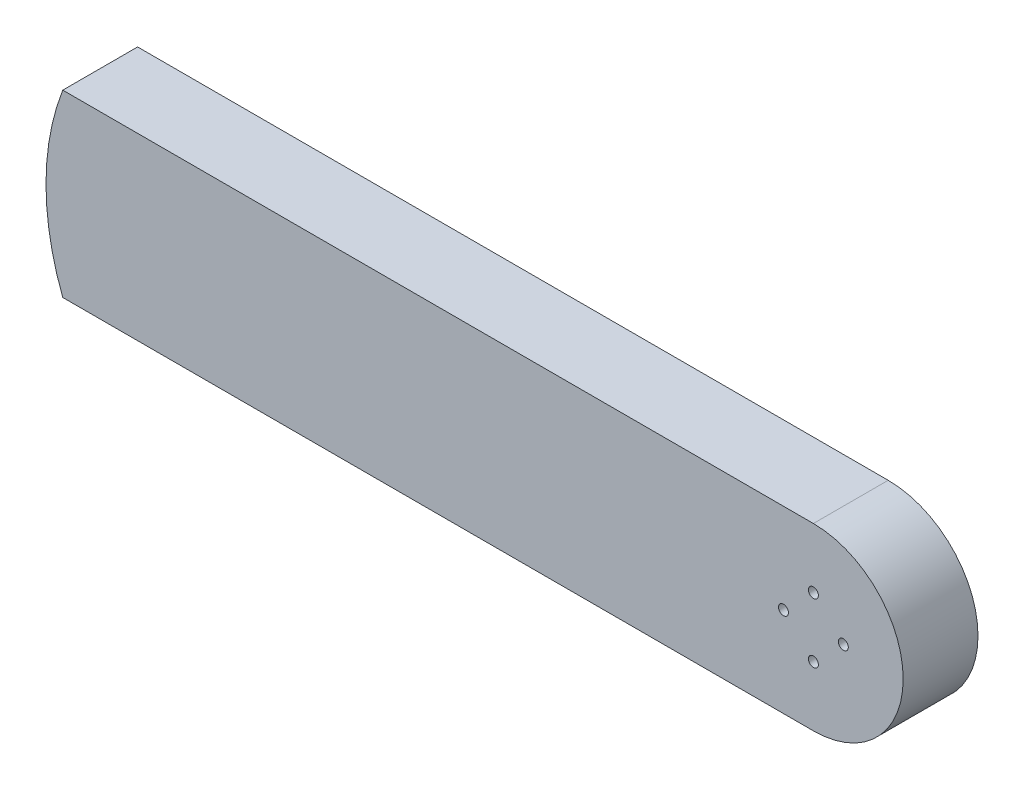
SolidWorks part; units mm, degrees
ref_plane "前视基准面" through (0, 0, 0) normal (0, 0, 1) x (1, 0, 0)
ref_plane "上视基准面" through (0, 0, 0) normal (0, 1, 0) x (1, 0, 0)
ref_plane "右视基准面" through (0, 0, 0) normal (1, 0, 0) x (0, 0, -1)
other "Configuration Table"
sketch "草图1" plane through (0, 0, 0) normal (0, 0, 1) x (1, 0, 0)
  line L1 (0, 0) -> (300, 0)
  line L2 (0, 0) -> (0, 36)
  line L3 (0, 36) -> (300, 36)
  line L4 (300, 0) -> (300, 36)
  dimension "D1" = 300
  dimension "D2" = 36
extrude "凸台-拉伸1" add sketch "草图1" along normal blind 15
sketch "草图2" plane through (0, 0, 0) normal (0, 0, 1) x (1, 0, 0)
  line L0 (0, 18) -> (6, 18) construction
  line L1 (0, 36) -> (0, 0) construction
  line L2 (49.87, 18) -> (49.87, 38.3624) construction
  line L3 (49.87, 18) -> (49.87, -29.0061) construction
  line L4 (6, 18) -> (91.74, 18) construction
  line L5 (91.74, 18) -> (93.74, 18) construction
  line L6 (300, 36) -> (0, 36) construction
  arc A2 (0.0194, 19.3902) -> (2.9047, 34.7712) centre (49.87, 18) cw
  arc A12 (92.7291, 17.0329) -> (91.0524, 6.0902) centre (49.87, 18) cw
  arc A13 (91.0413, 29.9482) -> (92.728, 19.0122) centre (49.87, 18) cw
  arc A14 (7.0167, 19.195) -> (9.4969, 32.4171) centre (49.87, 18) cw
  arc A15 (9.9258, 2.4341) -> (7.0814, 15.3593) centre (49.87, 18) cw
  circle A16 centre (9.0186, 5) radius 1
  circle A17 centre (7, 18) radius 1
  circle A18 centre (9.0186, 31) radius 1
  circle A19 centre (90.7214, 5) radius 1
  circle A20 centre (90.7214, 31) radius 1
  circle A21 centre (92.74, 18) radius 1
  point P52 (39.8387, 16.5659)
  dimension "D1" = 42.87
  dimension "D2" = 42.87
  dimension "D4" = 2
  dimension "D5" = 2
  dimension "D6" = 2
  dimension "D7" = 2
  dimension "D8" = 2
  dimension "D9" = 13
  dimension "D10" = 13
  dimension "D11" = 13
  dimension "D3" = 2
  dimension "D14" = 42.87
  dimension "D15" = 42.87
  dimension "D12" = 13
  dimension "D13" = 7
  dimension "D16" = 32.87
  dimension "D17" = 18
extrude "切除-拉伸2" cut sketch "草图2" along normal blind 5 contours A17 | A16 A15 | A20 | A16 A15 | A18 | A19 | A21 region at (8.6162, 4.8719, 0) region at (9.425, 5.1293, 0) region at (7, 18, 0) region at (90.7214, 31, 0)
sketch "草图3" plane through (0, 0, 0) normal (0, 0, -1) x (-1, 0, 0)
  line L0 (0, 18) -> (-6, 18) construction
  line L1 (0, 18) -> (-224.1604, 18) construction
  line L3 (-153.8297, 28) -> (-162.4899, 23)
  line L4 (-162.4899, 23) -> (-162.4899, 13)
  line L5 (-162.4899, 13) -> (-153.8297, 8)
  line L6 (-153.8297, 8) -> (-145.1694, 13)
  line L7 (-145.1694, 13) -> (-145.1694, 23)
  line L8 (-145.1694, 23) -> (-153.8297, 28)
  circle A0 centre (-153.8297, 18) radius 10
  circle A1 centre (-153.8297, 18) radius 8.6603 construction
  circle A3 centre (-153.8297, 18) radius 18
  point P2 (-153.8297, 18)
  point P20 (-256.8302, 18)
  dimension "D2" = 20
  dimension "D1" = 114
extrude "切除-拉伸3" cut sketch "草图3" against normal blind 10 contours L7 L8 L3 L4 L5 L6 region at (153.8297, 18, 0)
sketch "草图4" plane through (0, 0, 15) normal (0, 0, 1) x (1, 0, 0)
  line L0 (300, 36) -> (0, 36) construction
  line L1 (0, 0) -> (300, 0) construction
  line L4 (0, 36) -> (0, 0)
  line L5 (0, 0) -> (300, 0)
  line L6 (300, 0) -> (300, 36)
  line L7 (300, 36) -> (0, 36)
  line L8 (0, 36) -> (0, 0)
  line L9 (153.8297, 0) -> (300, 0)
  line L10 (300, 0) -> (300, 36)
  line L11 (300, 36) -> (153.8297, 36)
  arc A2 (153.8297, 0) -> (153.8297, 36) centre (153.8297, 18) ccw
  circle A3 centre (153.8297, 18) radius 18 construction
  line M6 (0, 0) -> (300, 0)
  line M7 (300, 0) -> (300, 36)
  line M8 (300, 36) -> (0, 36)
  dimension "D1" = 0
extrude "切除-拉伸4" cut sketch "草图4" against normal up to next contours A2 M6 M7 M8 region at (233.9223, 18, 15)
sketch "草图5" plane through (0, 0, 10) normal (0, 0, -1) x (-1, 0, 0)
  arc A0 (-153.8297, 36) -> (-153.8297, 0) centre (-153.8297, 18) ccw construction
  arc A1 (-153.8297, 36) -> (-153.8297, 0) centre (-153.8297, 18) ccw
  circle A2 centre (-153.8297, 18) radius 6 construction
  circle A3 centre (-153.8297, 24) radius 1
  circle A4 centre (-233.87, 102.5) radius 1
  circle A5 centre (-155.37, 182.5403) radius 1
  circle A6 centre (-75.3297, 104.0403) radius 1
  circle A7 centre (-146.3297, -68.0403) radius 1
  circle A8 centre (-238.37, -75.5403) radius 1
  circle A9 centre (-245.87, 16.5) radius 1
  circle A10 centre (-147.8297, 18) radius 1
  circle A11 centre (-159.8297, 18) radius 1
  circle A12 centre (-153.8297, 12) radius 1
  point P15 (-154.5998, 103.2702)
  point P22 (-196.0998, -25.7702)
  dimension "D1" = 12
  dimension "D2" = 2
  dimension "D5" = 2
  dimension "D6" = 2
  dimension "D7" = 2
  dimension "D3" = 4
  dimension "D4" = 4
extrude "切除-拉伸5" cut sketch "草图5" along direction (0, 0, -1) on the side against the normal blind 5 contours A12 | A11 | A3 | A10 region at (153.8297, 12, 10)
sketch "草图6" plane through (0, 0, 0) normal (0, 0, -1) x (-1, 0, 0)
  line L4 (-3.3618, 0) -> (0, 0)
  line L9 (0, 36) -> (-153.8297, 36)
  line L10 (-153.8297, 0) -> (0, 0)
  line L11 (0, 0) -> (0, 36)
  line L12 (0, 36) -> (-3.3618, 36)
  line L14 (0, 0) -> (0, 36)
  arc A6 (-3.3618, 0) -> (-3.3618, 36) centre (-49.87, 18) ccw
  arc A7 (-153.8297, 36) -> (-153.8297, 0) centre (-153.8297, 18) ccw
  arc A8 (-153.8297, 36) -> (-153.8297, 0) centre (-153.8297, 18) ccw
  line M17 (0, 36) -> (-153.8297, 36)
  line M19 (-153.8297, 0) -> (0, 0)
  line M20 (0, 0) -> (0, 36)
  dimension "D1" = 0
extrude "切除-拉伸6" cut sketch "草图6" against normal up to next contours M17 | M19 M20 region at (1.0024, 4.4691, 0) region at (1.0024, 31.5309, 0)
